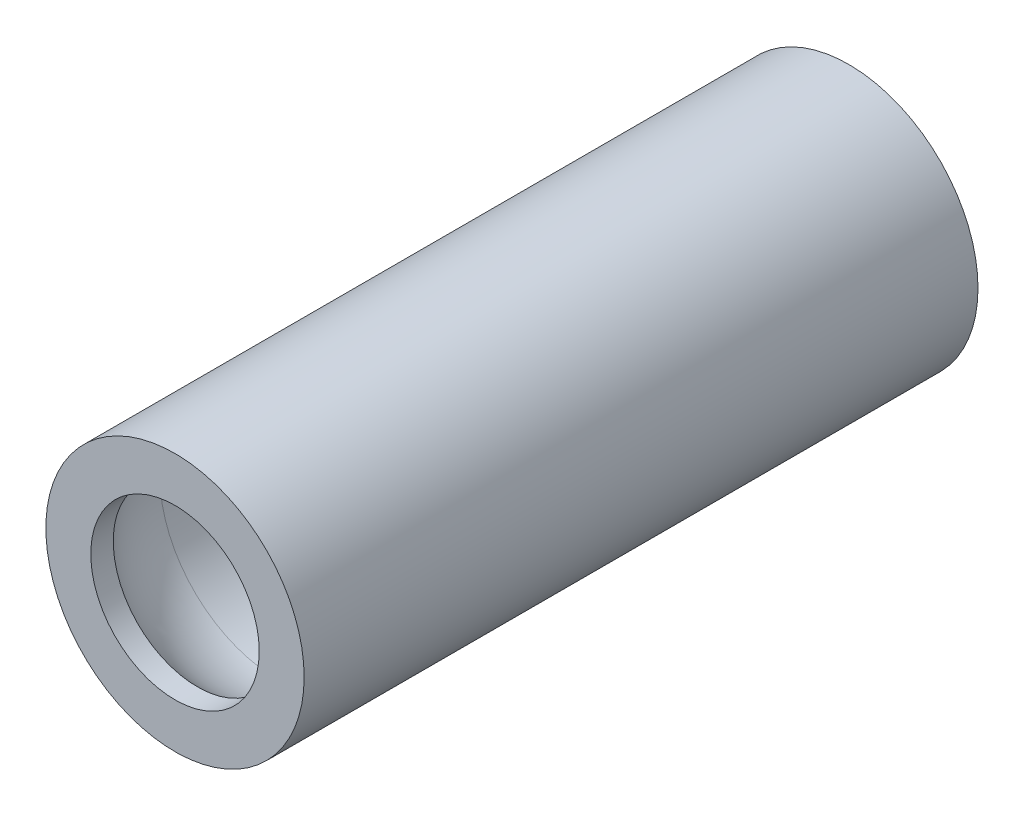
SolidWorks part; units mm, degrees
ref_plane "Front Plane" through (0, 0, 0) normal (0, 0, 1) x (1, 0, 0)
ref_plane "Top Plane" through (0, 0, 0) normal (0, 1, 0) x (1, 0, 0)
ref_plane "Right Plane" through (0, 0, 0) normal (1, 0, 0) x (0, 0, -1)
sketch "Sketch1" plane through (0, 0, 0) normal (0, 0, 1) x (1, 0, 0)
  line L0 (-7.5, 0) -> (-11.5, 0) construction
  line L1 (0, 10.5) -> (0, 11.5) construction
  circle A0 centre (0, 0) radius 7.5
  circle A1 centre (0, 0) radius 11.5
  circle A2 centre (0, 0) radius 10.5
  dimension "D1" = 15
  dimension "D2" = 4
  dimension "D3" = 1
extrude "Boss-Extrude1" add sketch "Sketch1" along normal blind 60 contours A1 A2 region at (-11.1747, 0, 0)
extrude "Boss-Extrude2" add sketch "Sketch1<3>" along normal blind 2 contours A2 A0 region at (-10.203, 0, 0)
sketch "Sketch1<3>" plane through (0, 0, 0) normal (0, 0, 1) x (1, 0, 0) same geometry as "Sketch1"
ref_plane "Plane1" through (0, 0, 30) normal (0, 0, 1) x (1, 0, 0)
mirror "Mirror1" about plane through (0, 0, 30) normal (0, 0, 1) of "Boss-Extrude2"
fillet "Fillet2" radius 10 2 edges at (10.5, 0, 2) (-10.5, 0, 58)
